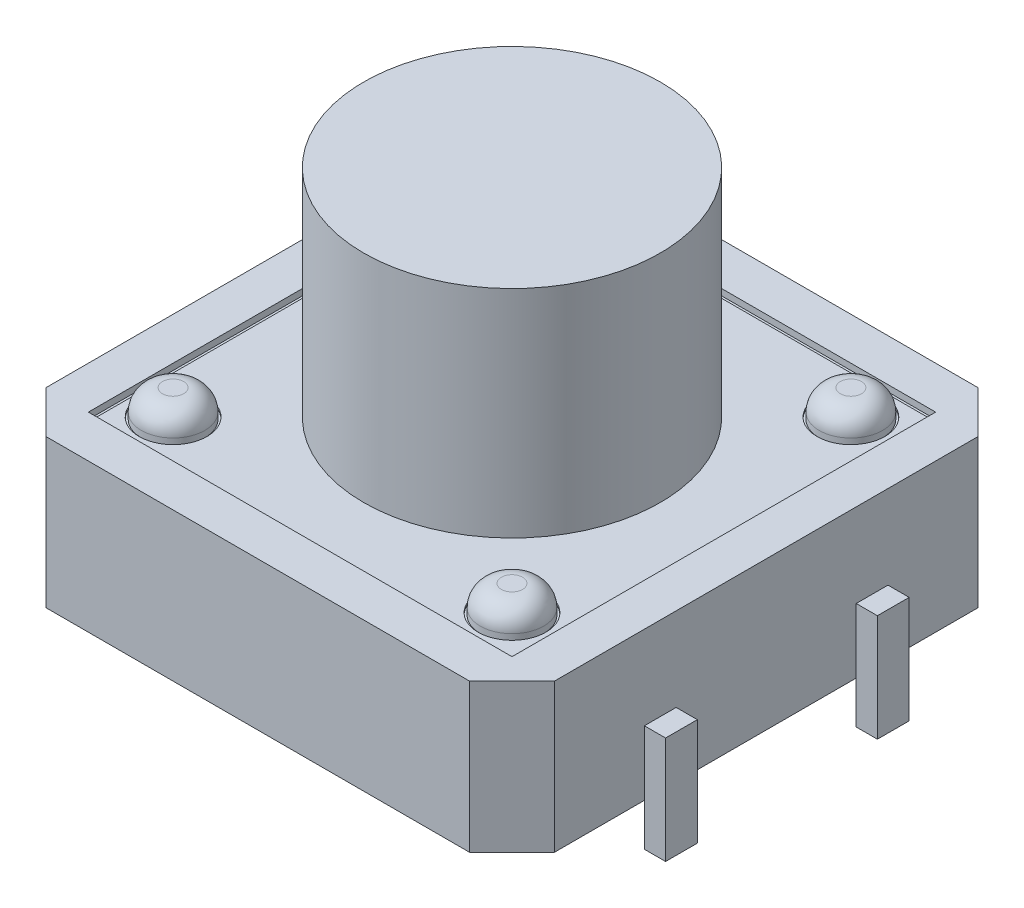
SolidWorks part; units mm, degrees
note: The reader was unsure of these and kept them because the rebuilt part matched: thickness of "Base-Flange1".
ref_plane "Front Plane" through (0, 0, 0) normal (0, 0, 1) x (1, 0, 0)
ref_plane "Top Plane" through (0, 0, 0) normal (0, 1, 0) x (1, 0, 0)
ref_plane "Right Plane" through (0, 0, 0) normal (1, 0, 0) x (0, 0, -1)
sketch "Sketch1" plane through (0, 0, 0) normal (0, 1, 0) x (1, 0, 0)
  line L1 (-6, -6) -> (6, -6)
  line L2 (-6, -6) -> (-6, 6)
  line L3 (-6, 6) -> (6, 6)
  line L4 (6, -6) -> (6, 6)
  line L5 (-6, -6) -> (6, 6) construction
  line L6 (-6, 6) -> (6, -6) construction
  point P0 (0, 0)
  dimension "D1" = 12
  dimension "D2" = 12
extrude "Boss-Extrude1" add sketch "Sketch1" along normal blind 3.5
sketch "Sketch15" plane through (0, 3.5, 0) normal (0, 1, 0) x (1, 0, 0)
  line L24 (5, 5) -> (-5, 5)
  line L26 (-5, 5) -> (-5, -5)
  line L28 (-5, -5) -> (5, -5)
  line L30 (5, -5) -> (5, 5)
  line L32 (5, 5) -> (-5, 5)
  line L34 (-5, 5) -> (-5, -5)
  line L36 (-5, -5) -> (5, -5)
  line L38 (5, -5) -> (5, 5)
  dimension "D1" = 1
extrude "Cut-Extrude1" cut sketch "Sketch15" against normal blind 0.15 normal cut yes
sketch "Sketch2" plane through (0, 3.5, 0) normal (0, 1, 0) x (1, 0, 0)
  circle A0 centre (0, 0) radius 3.5
  dimension "D1" = 7
extrude "Boss-Extrude2" add sketch "Sketch2" along normal blind 5 and the other way up to surface (3.5 mm away)
chamfer "Chamfer1" distance 1 angle 45 4 edges at (6, 1.75, 6) (-6, 1.75, -6) (6, 1.75, -6) (-6, 1.75, 6)
ref_plane "Plane1" through (0, 0, 0) normal (0, 0, 1) x (1, 0, 0)
ref_plane "Plane2" through (0, 0, 2.5) normal (0, 0, 1) x (1, 0, 0)
ref_plane "Plane3" through (0, 0, 0) normal (1, 0, 0) x (0, 0, -1)
sketch "Sketch4" plane through (0, 0, 2.5) normal (0, 0, 1) x (1, 0, 0)
  line L1 (6, 1.5251) -> (6, -1)
  line L4 (6, 3.5) -> (6, 0) construction
  line L5 (-5, 0) -> (5, 0) construction
  dimension "D1" = 1
base flange "Base-Flange1" sketch "Sketch4" end condition mid plane depth 0.75 reverse direction no thickness 0.5 reverse thickness direction yes bend radius 0.05
mirror "Mirror1" about plane through (0, 0, 0) normal (0, 0, 1) of bodies 103
mirror "Mirror2" about plane through (0, 0, 0) normal (1, 0, 0) of bodies 103 104
sketch "Sketch16" plane through (0, 3.35, 0) normal (0, 1, 0) x (1, 0, 0)
  line L0 (5, 5) -> (-5, 5) construction
  line L1 (-5, 5) -> (-5, -5) construction
  line L2 (0, 5) -> (0, -5) construction
  line L3 (5, 5) -> (-5, 5) construction
  line L4 (-5, -5) -> (5, -5) construction
  line L6 (-5, 0) -> (5, 0) construction
  line L7 (5, -5) -> (5, 5) construction
  circle A0 centre (-4, 4) radius 0.75
  circle A1 centre (4, 4) radius 0.75
  circle A2 centre (4, -4) radius 0.75
  circle A3 centre (-4, -4) radius 0.75
  dimension "D2" = 1.5
  dimension "D1" = 1
  dimension "D3" = 1
extrude "Boss-Extrude3" add sketch "Sketch16" along normal blind 0.65
fillet "Fillet1" radius 0.5 4 edges at (4, 4, -4.75) (4, 4, 4.75) (-4, 4, -3.25) (-4, 4, 3.25)
sketch "Sketch17" plane through (0, 3.35, 0) normal (0, 1, 0) x (1, 0, 0)
  line L30 (-4.9, -4.9) -> (4.9, -4.9)
  line L31 (4.9, -4.9) -> (4.9, 4.9)
  line L32 (4.9, 4.9) -> (-4.9, 4.9)
  line L33 (-4.9, 4.9) -> (-4.9, -4.9)
  line L34 (-4.9, -4.9) -> (4.9, -4.9)
  line L35 (4.9, -4.9) -> (4.9, 4.9)
  line L36 (4.9, 4.9) -> (-4.9, 4.9)
  line L37 (-4.9, 4.9) -> (-4.9, -4.9)
  circle A11 centre (-4, 4) radius 0.8
  circle A12 centre (-4, 4) radius 0.8
  circle A14 centre (4, 4) radius 0.8
  circle A15 centre (4, 4) radius 0.8
  circle A17 centre (-4, -4) radius 0.8
  circle A18 centre (-4, -4) radius 0.8
  circle A20 centre (4, -4) radius 0.8
  circle A21 centre (4, -4) radius 0.8
  dimension "D1" = 0.1
  dimension "D2" = 0.05
  dimension "D3" = 0.05
  dimension "D4" = 0.05
  dimension "D5" = 0.05
extrude "Boss-Extrude4" add sketch "Sketch17" along normal blind 0.05
sketch "Bend-Lines1" plane through (0, 0, 0) normal (0, 1, 0) x (1, 0, 0)
sketch "Bounding-Box1" plane through (0, 0, 0) normal (0, 1, 0) x (1, 0, 0)
sheet metal parameters "Sheet-Metal3" thickness 0.5 parameters "D1"=0.05
flat pattern "Flat-Pattern3" [suppressed]
sketch "Bend-Lines2" plane through (0, 0, 0) normal (0, 1, 0) x (1, 0, 0)
sketch "Bounding-Box2" [suppressed] plane through (0, 0, 0) normal (0, 1, 0) x (1, 0, 0)
sheet metal parameters "Sheet-Metal4" thickness 0.5 parameters "D1"=0.05
flat pattern "Flat-Pattern4"
sketch "Bend-Lines3" plane through (0, 0, 0) normal (0, 1, 0) x (1, 0, 0)
sketch "Bounding-Box3" [suppressed] plane through (0, 0, 0) normal (0, 1, 0) x (1, 0, 0)
sheet metal parameters "Sheet-Metal5" thickness 0.5 parameters "D1"=0.05
flat pattern "Flat-Pattern5"
sketch "Bend-Lines4" plane through (0, 0, 0) normal (0, 1, 0) x (1, 0, 0)
sketch "Bounding-Box4" [suppressed] plane through (0, 0, 0) normal (0, 1, 0) x (1, 0, 0)
sheet metal parameters "Sheet-Metal6" thickness 0.5 parameters "D1"=0.05
flat pattern "Flat-Pattern6"
sketch "Bend-Lines5" plane through (0, 0, 0) normal (0, 1, 0) x (1, 0, 0)
sketch "Bounding-Box5" [suppressed] plane through (0, 0, 0) normal (0, 1, 0) x (1, 0, 0)
